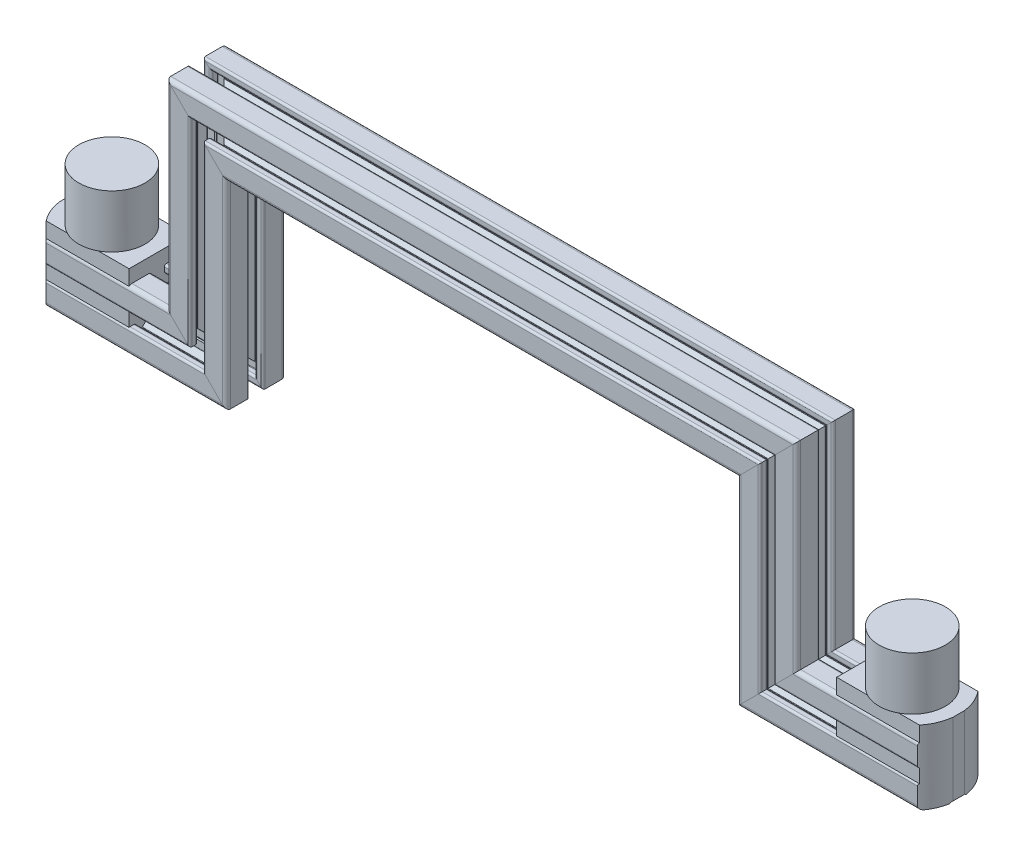
SolidWorks part; units mm, degrees
material "Commercially Pure CP-Ti UNS R50400 (SS)"
ref_plane "Front Plane" through (0, 0, 0) normal (0, 0, 1) x (1, 0, 0)
ref_plane "Top Plane" through (0, 0, 0) normal (0, 1, 0) x (1, 0, 0)
ref_plane "Right Plane" through (0, 0, 0) normal (1, 0, 0) x (0, 0, -1)
sketch "Sketch7" plane through (0, 0, 0) normal (1, 0, 0) x (0, 0, -1)
  line L0 (13.9698, 21.2743) -> (13.5298, 21.2743)
  line L1 (12.0298, 22.7743) -> (12.0298, 23.2743)
  line L2 (13.5298, 24.7743) -> (23.1398, 24.7743)
  line L3 (25.4198, 22.4943) -> (25.4198, 12.8843)
  line L4 (23.9198, 11.3843) -> (23.4198, 11.3843)
  line L5 (21.9198, 12.8843) -> (21.9198, 13.3243)
  line L6 (20.9198, 14.3243) -> (15.3498, 14.3243)
  line L7 (14.9698, 14.7043) -> (14.9698, 20.2743)
  line L8 (21.9589, -6.6897) -> (21.9589, -6.2497)
  line L9 (23.4589, -4.7497) -> (23.9589, -4.7497)
  line L10 (25.4589, -6.2497) -> (25.4589, -15.8597)
  line L11 (23.1789, -18.1397) -> (13.5689, -18.1397)
  line L12 (12.0689, -16.6397) -> (12.0689, -16.1397)
  line L13 (13.5689, -14.6397) -> (14.0089, -14.6397)
  line L14 (15.0089, -13.6397) -> (15.0089, -8.0697)
  line L15 (15.3889, -7.6897) -> (20.9589, -7.6897)
  line L16 (-6.0052, -14.6787) -> (-5.5652, -14.6787)
  line L17 (-4.0652, -16.1787) -> (-4.0652, -16.6787)
  line L18 (-5.5652, -18.1787) -> (-15.1752, -18.1787)
  line L19 (-17.4552, -15.8987) -> (-17.4552, -6.2887)
  line L20 (-15.9552, -4.7887) -> (-15.4552, -4.7887)
  line L21 (-13.9552, -6.2887) -> (-13.9552, -6.7287)
  line L22 (-12.9552, -7.7287) -> (-7.3852, -7.7287)
  line L23 (-7.0052, -8.1087) -> (-7.0052, -13.6787)
  line L24 (1.8289, -2.4886) -> (1.4132, -2.3164)
  line L25 (-1.632, 0.7289) -> (-1.8042, 1.1447)
  line L26 (-1.804, 5.4512) -> (-1.6318, 5.867)
  line L27 (1.4134, 8.9121) -> (1.8292, 9.0843)
  line L28 (6.1358, 9.0842) -> (6.5515, 8.912)
  line L29 (9.5966, 5.8667) -> (9.7688, 5.451)
  line L30 (9.7687, 1.1444) -> (9.5965, 0.7287)
  line L31 (6.5512, -2.3165) -> (6.1355, -2.4887)
  line L32 (-13.9942, 13.2853) -> (-13.9942, 12.8453)
  line L33 (-15.4942, 11.3453) -> (-15.9942, 11.3453)
  line L34 (-17.4942, 12.8453) -> (-17.4942, 22.4553)
  line L35 (-15.2142, 24.7353) -> (-5.6042, 24.7353)
  line L36 (-4.1042, 23.2353) -> (-4.1042, 22.7353)
  line L37 (-5.6042, 21.2353) -> (-6.0442, 21.2353)
  line L38 (-7.0442, 20.2353) -> (-7.0442, 14.6653)
  line L39 (-7.4242, 14.2853) -> (-12.9942, 14.2853)
  line L40 (4.9058, 11.2153) -> (4.0058, 10.7002)
  line L41 (4.0058, 10.7002) -> (3.1058, 11.2153)
  line L42 (3.1058, 11.2153) -> (-2.1975, 11.2153)
  line L43 (-2.4662, 11.3266) -> (-5.9329, 14.7933)
  line L44 (-6.0442, 15.062) -> (-6.0442, 19.3553)
  line L45 (-5.6642, 19.7353) -> (-2.5792, 19.7353)
  line L46 (-1.0592, 21.2553) -> (-1.0592, 24.2153)
  line L47 (-2.5792, 25.7353) -> (-15.4942, 25.7353)
  line L48 (-18.4942, 22.7353) -> (-18.4942, 9.8203)
  line L49 (-16.9742, 8.3003) -> (-14.0142, 8.3003)
  line L50 (-12.4942, 9.8203) -> (-12.4942, 12.9053)
  line L51 (-12.1142, 13.2853) -> (-7.8138, 13.2853)
  line L52 (-7.5451, 13.174) -> (-4.0855, 9.7144)
  line L53 (-3.9742, 9.4457) -> (-3.9742, 4.1353)
  line L54 (-3.9742, 4.1353) -> (-3.4546, 3.2353)
  line L55 (-3.4546, 3.2353) -> (-3.9742, 2.3353)
  line L56 (-3.9742, 2.3353) -> (-3.9742, -2.968)
  line L57 (-4.0855, -3.2367) -> (-7.5522, -6.7034)
  line L58 (-7.8209, -6.8147) -> (-12.1142, -6.8147)
  line L59 (-12.4942, -6.4347) -> (-12.4942, -3.3497)
  line L60 (-14.0142, -1.8297) -> (-16.9742, -1.8297)
  line L61 (-18.4942, -3.3497) -> (-18.4942, -16.2647)
  line L62 (-15.4942, -19.2647) -> (-2.5792, -19.2647)
  line L63 (-1.0592, -17.7447) -> (-1.0592, -14.7847)
  line L64 (-2.5792, -13.2647) -> (-5.6642, -13.2647)
  line L65 (-6.0442, -12.8847) -> (-6.0442, -8.5843)
  line L66 (-5.9329, -8.3156) -> (-2.4733, -4.856)
  line L67 (-2.2046, -4.7447) -> (3.1058, -4.7447)
  line L68 (3.1058, -4.7447) -> (4.0058, -4.2295)
  line L69 (4.0058, -4.2295) -> (4.9058, -4.7447)
  line L70 (4.9058, -4.7447) -> (10.2091, -4.7447)
  line L71 (10.4778, -4.856) -> (13.9445, -8.3227)
  line L72 (14.0558, -8.5914) -> (14.0558, -12.8847)
  line L73 (13.6758, -13.2647) -> (10.5908, -13.2647)
  line L74 (9.0708, -14.7847) -> (9.0708, -17.7447)
  line L75 (10.5908, -19.2647) -> (23.5058, -19.2647)
  line L76 (26.5058, -16.2647) -> (26.5058, -3.3497)
  line L77 (24.9858, -1.8297) -> (22.0258, -1.8297)
  line L78 (20.5058, -3.3497) -> (20.5058, -6.4347)
  line L79 (20.1258, -6.8147) -> (15.8254, -6.8147)
  line L80 (15.5567, -6.7034) -> (12.0971, -3.2438)
  line L81 (11.9858, -2.9751) -> (11.9858, 2.3353)
  line L82 (11.9858, 2.3353) -> (11.4662, 3.2353)
  line L83 (11.4662, 3.2353) -> (11.9858, 4.1353)
  line L84 (11.9858, 4.1353) -> (11.9858, 9.4386)
  line L85 (12.0971, 9.7073) -> (15.5638, 13.174)
  line L86 (15.8325, 13.2853) -> (20.1258, 13.2853)
  line L87 (20.5058, 12.9053) -> (20.5058, 9.8203)
  line L88 (22.0258, 8.3003) -> (24.9858, 8.3003)
  line L89 (26.5058, 9.8203) -> (26.5058, 22.7353)
  line L90 (23.5058, 25.7353) -> (10.5908, 25.7353)
  line L91 (9.0708, 24.2153) -> (9.0708, 21.2553)
  line L92 (10.5908, 19.7353) -> (13.6758, 19.7353)
  line L93 (14.0558, 19.3553) -> (14.0558, 15.0549)
  line L94 (13.9445, 14.7862) -> (10.4849, 11.3266)
  line L95 (10.2162, 11.2153) -> (4.9058, 11.2153)
  arc A0 (14.9698, 20.2743) -> (13.9698, 21.2743) centre (13.9698, 20.2743) ccw
  arc A1 (12.0298, 22.7743) -> (13.5298, 21.2743) centre (13.5298, 22.7743) ccw
  arc A2 (13.5298, 24.7743) -> (12.0298, 23.2743) centre (13.5298, 23.2743) ccw
  arc A3 (25.4198, 22.4943) -> (23.1398, 24.7743) centre (23.1398, 22.4943) ccw
  arc A4 (23.9198, 11.3843) -> (25.4198, 12.8843) centre (23.9198, 12.8843) ccw
  arc A5 (21.9198, 12.8843) -> (23.4198, 11.3843) centre (23.4198, 12.8843) ccw
  arc A6 (21.9198, 13.3243) -> (20.9198, 14.3243) centre (20.9198, 13.3243) ccw
  arc A7 (14.9698, 14.7043) -> (15.3498, 14.3243) centre (15.3498, 14.7043) ccw
  arc A8 (20.9589, -7.6897) -> (21.9589, -6.6897) centre (20.9589, -6.6897) ccw
  arc A9 (23.4589, -4.7497) -> (21.9589, -6.2497) centre (23.4589, -6.2497) ccw
  arc A10 (25.4589, -6.2497) -> (23.9589, -4.7497) centre (23.9589, -6.2497) ccw
  arc A11 (23.1789, -18.1397) -> (25.4589, -15.8597) centre (23.1789, -15.8597) ccw
  arc A12 (12.0689, -16.6397) -> (13.5689, -18.1397) centre (13.5689, -16.6397) ccw
  arc A13 (13.5689, -14.6397) -> (12.0689, -16.1397) centre (13.5689, -16.1397) ccw
  arc A14 (14.0089, -14.6397) -> (15.0089, -13.6397) centre (14.0089, -13.6397) ccw
  arc A15 (15.3889, -7.6897) -> (15.0089, -8.0697) centre (15.3889, -8.0697) ccw
  arc A16 (-7.0052, -13.6787) -> (-6.0052, -14.6787) centre (-6.0052, -13.6787) ccw
  arc A17 (-4.0652, -16.1787) -> (-5.5652, -14.6787) centre (-5.5652, -16.1787) ccw
  arc A18 (-5.5652, -18.1787) -> (-4.0652, -16.6787) centre (-5.5652, -16.6787) ccw
  arc A19 (-17.4552, -15.8987) -> (-15.1752, -18.1787) centre (-15.1752, -15.8987) ccw
  arc A20 (-15.9552, -4.7887) -> (-17.4552, -6.2887) centre (-15.9552, -6.2887) ccw
  arc A21 (-13.9552, -6.2887) -> (-15.4552, -4.7887) centre (-15.4552, -6.2887) ccw
  arc A22 (-13.9552, -6.7287) -> (-12.9552, -7.7287) centre (-12.9552, -6.7287) ccw
  arc A23 (-7.0052, -8.1087) -> (-7.3852, -7.7287) centre (-7.3852, -8.1087) ccw
  arc A24 (1.0363, -0.7421) -> (1.4132, -2.3164) centre (1.7959, -1.3925) ccw
  arc A25 (-0.0577, 0.352) -> (1.0363, -0.7421) centre (3.9823, 3.2978) ccw
  arc A26 (-1.632, 0.7289) -> (-0.0577, 0.352) centre (-0.7081, 1.1116) ccw
  arc A27 (-0.9575, 2.5244) -> (-1.8042, 1.1447) centre (-0.8803, 1.5274) ccw
  arc A28 (-0.9574, 4.0715) -> (-0.9575, 2.5244) centre (3.9823, 3.2978) ccw
  arc A29 (-1.804, 5.4512) -> (-0.9574, 4.0715) centre (-0.8802, 5.0686) ccw
  arc A30 (-0.0575, 6.2439) -> (-1.6318, 5.867) centre (-0.708, 5.4843) ccw
  arc A31 (1.0365, 7.3379) -> (-0.0575, 6.2439) centre (3.9823, 3.2978) ccw
  arc A32 (1.4134, 8.9121) -> (1.0365, 7.3379) centre (1.7961, 7.9882) ccw
  arc A33 (3.2089, 8.2376) -> (1.8292, 9.0843) centre (2.2119, 8.1604) ccw
  arc A34 (4.7561, 8.2376) -> (3.2089, 8.2376) centre (3.9823, 3.2978) ccw
  arc A35 (6.1358, 9.0842) -> (4.7561, 8.2376) centre (5.7531, 8.1603) ccw
  arc A36 (6.9284, 7.3377) -> (6.5515, 8.912) centre (6.1688, 7.9881) ccw
  arc A37 (8.0224, 6.2437) -> (6.9284, 7.3377) centre (3.9823, 3.2978) ccw
  arc A38 (9.5966, 5.8667) -> (8.0224, 6.2437) centre (8.6727, 5.484) ccw
  arc A39 (8.9222, 4.0713) -> (9.7688, 5.451) centre (8.845, 5.0683) ccw
  arc A40 (8.9221, 2.5241) -> (8.9222, 4.0713) centre (3.9823, 3.2978) ccw
  arc A41 (9.7687, 1.1444) -> (8.9221, 2.5241) centre (8.8448, 1.5271) ccw
  arc A42 (8.0222, 0.3518) -> (9.5965, 0.7287) centre (8.6726, 1.1113) ccw
  arc A43 (6.9282, -0.7422) -> (8.0222, 0.3518) centre (3.9823, 3.2978) ccw
  arc A44 (6.5512, -2.3165) -> (6.9282, -0.7422) centre (6.1685, -1.3926) ccw
  arc A45 (4.7558, -1.642) -> (6.1355, -2.4887) centre (5.7528, -1.5648) ccw
  arc A46 (3.2086, -1.642) -> (4.7558, -1.642) centre (3.9823, 3.2978) ccw
  arc A47 (1.8289, -2.4886) -> (3.2086, -1.642) centre (2.2116, -1.5647) ccw
  arc A48 (-12.9942, 14.2853) -> (-13.9942, 13.2853) centre (-12.9942, 13.2853) ccw
  arc A49 (-15.4942, 11.3453) -> (-13.9942, 12.8453) centre (-15.4942, 12.8453) ccw
  arc A50 (-17.4942, 12.8453) -> (-15.9942, 11.3453) centre (-15.9942, 12.8453) ccw
  arc A51 (-15.2142, 24.7353) -> (-17.4942, 22.4553) centre (-15.2142, 22.4553) ccw
  arc A52 (-4.1042, 23.2353) -> (-5.6042, 24.7353) centre (-5.6042, 23.2353) ccw
  arc A53 (-5.6042, 21.2353) -> (-4.1042, 22.7353) centre (-5.6042, 22.7353) ccw
  arc A54 (-6.0442, 21.2353) -> (-7.0442, 20.2353) centre (-6.0442, 20.2353) ccw
  arc A55 (-7.4242, 14.2853) -> (-7.0442, 14.6653) centre (-7.4242, 14.6653) ccw
  arc A56 (-2.4662, 11.3266) -> (-2.1975, 11.2153) centre (-2.1975, 11.5953) ccw
  arc A57 (-6.0442, 15.062) -> (-5.9329, 14.7933) centre (-5.6642, 15.062) ccw
  arc A58 (-5.6642, 19.7353) -> (-6.0442, 19.3553) centre (-5.6642, 19.3553) ccw
  arc A59 (-2.5792, 19.7353) -> (-1.0592, 21.2553) centre (-2.5792, 21.2553) ccw
  arc A60 (-1.0592, 24.2153) -> (-2.5792, 25.7353) centre (-2.5792, 24.2153) ccw
  arc A61 (-15.4942, 25.7353) -> (-18.4942, 22.7353) centre (-15.4942, 22.7353) ccw
  arc A62 (-18.4942, 9.8203) -> (-16.9742, 8.3003) centre (-16.9742, 9.8203) ccw
  arc A63 (-14.0142, 8.3003) -> (-12.4942, 9.8203) centre (-14.0142, 9.8203) ccw
  arc A64 (-12.1142, 13.2853) -> (-12.4942, 12.9053) centre (-12.1142, 12.9053) ccw
  arc A65 (-7.5451, 13.174) -> (-7.8138, 13.2853) centre (-7.8138, 12.9053) ccw
  arc A66 (-3.9742, 9.4457) -> (-4.0855, 9.7144) centre (-4.3542, 9.4457) ccw
  arc A67 (-4.0855, -3.2367) -> (-3.9742, -2.968) centre (-4.3542, -2.968) ccw
  arc A68 (-7.8209, -6.8147) -> (-7.5522, -6.7034) centre (-7.8209, -6.4347) ccw
  arc A69 (-12.4942, -6.4347) -> (-12.1142, -6.8147) centre (-12.1142, -6.4347) ccw
  arc A70 (-12.4942, -3.3497) -> (-14.0142, -1.8297) centre (-14.0142, -3.3497) ccw
  arc A71 (-16.9742, -1.8297) -> (-18.4942, -3.3497) centre (-16.9742, -3.3497) ccw
  arc A72 (-18.4942, -16.2647) -> (-15.4942, -19.2647) centre (-15.4942, -16.2647) ccw
  arc A73 (-2.5792, -19.2647) -> (-1.0592, -17.7447) centre (-2.5792, -17.7447) ccw
  arc A74 (-1.0592, -14.7847) -> (-2.5792, -13.2647) centre (-2.5792, -14.7847) ccw
  arc A75 (-6.0442, -12.8847) -> (-5.6642, -13.2647) centre (-5.6642, -12.8847) ccw
  arc A76 (-5.9329, -8.3156) -> (-6.0442, -8.5843) centre (-5.6642, -8.5843) ccw
  arc A77 (-2.2046, -4.7447) -> (-2.4733, -4.856) centre (-2.2046, -5.1247) ccw
  arc A78 (10.4778, -4.856) -> (10.2091, -4.7447) centre (10.2091, -5.1247) ccw
  arc A79 (14.0558, -8.5914) -> (13.9445, -8.3227) centre (13.6758, -8.5914) ccw
  arc A80 (13.6758, -13.2647) -> (14.0558, -12.8847) centre (13.6758, -12.8847) ccw
  arc A81 (10.5908, -13.2647) -> (9.0708, -14.7847) centre (10.5908, -14.7847) ccw
  arc A82 (9.0708, -17.7447) -> (10.5908, -19.2647) centre (10.5908, -17.7447) ccw
  arc A83 (23.5058, -19.2647) -> (26.5058, -16.2647) centre (23.5058, -16.2647) ccw
  arc A84 (26.5058, -3.3497) -> (24.9858, -1.8297) centre (24.9858, -3.3497) ccw
  arc A85 (22.0258, -1.8297) -> (20.5058, -3.3497) centre (22.0258, -3.3497) ccw
  arc A86 (20.1258, -6.8147) -> (20.5058, -6.4347) centre (20.1258, -6.4347) ccw
  arc A87 (15.5567, -6.7034) -> (15.8254, -6.8147) centre (15.8254, -6.4347) ccw
  arc A88 (11.9858, -2.9751) -> (12.0971, -3.2438) centre (12.3658, -2.9751) ccw
  arc A89 (12.0971, 9.7073) -> (11.9858, 9.4386) centre (12.3658, 9.4386) ccw
  arc A90 (15.8325, 13.2853) -> (15.5638, 13.174) centre (15.8325, 12.9053) ccw
  arc A91 (20.5058, 12.9053) -> (20.1258, 13.2853) centre (20.1258, 12.9053) ccw
  arc A92 (20.5058, 9.8203) -> (22.0258, 8.3003) centre (22.0258, 9.8203) ccw
  arc A93 (24.9858, 8.3003) -> (26.5058, 9.8203) centre (24.9858, 9.8203) ccw
  arc A94 (26.5058, 22.7353) -> (23.5058, 25.7353) centre (23.5058, 22.7353) ccw
  arc A95 (10.5908, 25.7353) -> (9.0708, 24.2153) centre (10.5908, 24.2153) ccw
  arc A96 (9.0708, 21.2553) -> (10.5908, 19.7353) centre (10.5908, 21.2553) ccw
  arc A97 (14.0558, 19.3553) -> (13.6758, 19.7353) centre (13.6758, 19.3553) ccw
  arc A98 (13.9445, 14.7862) -> (14.0558, 15.0549) centre (13.6758, 15.0549) ccw
  arc A99 (10.2162, 11.2153) -> (10.4849, 11.3266) centre (10.2162, 11.5953) ccw
sketch "Sketch1" plane through (0, 0, 0) normal (0, 0, 1) x (1, 0, 0)
  line L0 (0, 0) -> (125, 0)
  line L1 (125, 0) -> (125, 150)
  line L2 (125, 150) -> (337, 150)
  dimension "D1" = 337
  dimension "D2" = 125
  dimension "D3" = 150
sketch "Sketch2" [suppressed] plane through (0, 0, 0) normal (1, 0, 0) x (0, 0, -1)
  line L0 (-33.5, -41) -> (-31.5, -41)
  line L1 (-31.5, -43) -> (-42, -43)
  line L2 (-43, -42) -> (-43, -31.5)
  line L3 (-41, -31.5) -> (-41, -33.5)
  line L4 (-40, -34.5) -> (-34.88, -34.5)
  line L5 (-34.5, -34.88) -> (-34.5, -40)
  line L6 (-16.657, -26.2238) -> (-18.284, -25.188)
  line L7 (-19.8123, -26.7162) -> (-18.7764, -28.3429)
  line L8 (-21.0015, -29.2647) -> (-21.4195, -27.3819)
  line L9 (-23.5808, -27.3818) -> (-23.9986, -29.2645)
  line L10 (-26.2238, -28.343) -> (-25.188, -26.716)
  line L11 (-26.7162, -25.1877) -> (-28.3429, -26.2236)
  line L12 (-29.2647, -23.9985) -> (-27.3819, -23.5805)
  line L13 (-27.3818, -21.4192) -> (-29.2645, -21.0014)
  line L14 (-28.343, -18.7762) -> (-26.716, -19.812)
  line L15 (-25.1877, -18.2838) -> (-26.2236, -16.6571)
  line L16 (-23.9985, -15.7353) -> (-23.5805, -17.6181)
  line L17 (-21.4192, -17.6182) -> (-21.0014, -15.7355)
  line L18 (-18.7762, -16.657) -> (-19.812, -18.284)
  line L19 (-18.2838, -19.8123) -> (-16.6571, -18.7764)
  line L20 (-15.7353, -21.0015) -> (-17.6181, -21.4195)
  line L21 (-17.6182, -23.5808) -> (-15.7355, -23.9986)
  line L22 (41, -33.5) -> (41, -31.5)
  line L23 (43, -31.5) -> (43, -42)
  line L24 (42, -43) -> (31.5, -43)
  line L25 (31.5, -41) -> (33.5, -41)
  line L26 (34.5, -40) -> (34.5, -34.88)
  line L27 (34.88, -34.5) -> (40, -34.5)
  line L28 (26.7162, -19.8123) -> (28.3429, -18.7764)
  line L29 (29.2647, -21.0015) -> (27.3819, -21.4195)
  line L30 (27.3818, -23.5808) -> (29.2645, -23.9986)
  line L31 (28.343, -26.2238) -> (26.716, -25.188)
  line L32 (25.1877, -26.7162) -> (26.2236, -28.3429)
  line L33 (23.9985, -29.2647) -> (23.5805, -27.3819)
  line L34 (21.4192, -27.3818) -> (21.0014, -29.2645)
  line L35 (18.7762, -28.343) -> (19.812, -26.716)
  line L36 (18.2838, -25.1877) -> (16.6571, -26.2236)
  line L37 (15.7353, -23.9985) -> (17.6181, -23.5805)
  line L38 (17.6182, -21.4192) -> (15.7355, -21.0014)
  line L39 (16.657, -18.7762) -> (18.284, -19.812)
  line L40 (19.8123, -18.2838) -> (18.7764, -16.6571)
  line L41 (21.0015, -15.7353) -> (21.4195, -17.6181)
  line L42 (23.5808, -17.6182) -> (23.9986, -15.7355)
  line L43 (26.2238, -16.657) -> (25.188, -18.284)
  line L44 (34.5, 34.88) -> (34.5, 40)
  line L45 (33.5, 41) -> (31.5, 41)
  line L46 (31.5, 43) -> (42, 43)
  line L47 (43, 42) -> (43, 31.5)
  line L48 (41, 31.5) -> (41, 33.5)
  line L49 (40, 34.5) -> (34.88, 34.5)
  line L50 (26.7162, 25.1877) -> (28.3429, 26.2236)
  line L51 (29.2647, 23.9985) -> (27.3819, 23.5805)
  line L52 (27.3818, 21.4192) -> (29.2645, 21.0014)
  line L53 (28.343, 18.7762) -> (26.716, 19.812)
  line L54 (25.1877, 18.2838) -> (26.2236, 16.6571)
  line L55 (23.9985, 15.7353) -> (23.5805, 17.6181)
  line L56 (21.4192, 17.6182) -> (21.0014, 15.7355)
  line L57 (18.7762, 16.657) -> (19.812, 18.284)
  line L58 (18.2838, 19.8123) -> (16.6571, 18.7764)
  line L59 (15.7353, 21.0015) -> (17.6181, 21.4195)
  line L60 (17.6182, 23.5808) -> (15.7355, 23.9986)
  line L61 (16.657, 26.2238) -> (18.284, 25.188)
  line L62 (19.8123, 26.7162) -> (18.7764, 28.3429)
  line L63 (21.0015, 29.2647) -> (21.4195, 27.3819)
  line L64 (23.5808, 27.3818) -> (23.9986, 29.2645)
  line L65 (26.2238, 28.343) -> (25.188, 26.716)
  line L66 (-41, 33.5) -> (-41, 31.5)
  line L67 (-43, 31.5) -> (-43, 42)
  line L68 (-42, 43) -> (-31.5, 43)
  line L69 (-31.5, 41) -> (-33.5, 41)
  line L70 (-34.5, 40) -> (-34.5, 34.88)
  line L71 (-34.88, 34.5) -> (-40, 34.5)
  line L72 (-16.657, 18.7762) -> (-18.284, 19.812)
  line L73 (-19.8123, 18.2838) -> (-18.7764, 16.6571)
  line L74 (-21.0015, 15.7353) -> (-21.4195, 17.6181)
  line L75 (-23.5808, 17.6182) -> (-23.9986, 15.7355)
  line L76 (-26.2238, 16.657) -> (-25.188, 18.284)
  line L77 (-26.7162, 19.8123) -> (-28.3429, 18.7764)
  line L78 (-29.2647, 21.0015) -> (-27.3819, 21.4195)
  line L79 (-27.3818, 23.5808) -> (-29.2645, 23.9986)
  line L80 (-28.343, 26.2238) -> (-26.716, 25.188)
  line L81 (-25.1877, 26.7162) -> (-26.2236, 28.3429)
  line L82 (-23.9985, 29.2647) -> (-23.5805, 27.3819)
  line L83 (-21.4192, 27.3818) -> (-21.0014, 29.2645)
  line L84 (-18.7762, 28.343) -> (-19.812, 26.716)
  line L85 (-18.2838, 25.1877) -> (-16.6571, 26.2236)
  line L86 (-15.7353, 23.9985) -> (-17.6181, 23.5805)
  line L87 (-17.6182, 21.4192) -> (-15.7355, 21.0014)
  line L88 (39, -10.16) -> (33.3774, -10.16)
  line L89 (31.9632, -10.7458) -> (29.8203, -12.8887)
  line L90 (29.5516, -13) -> (23.4, -13)
  line L91 (23.4, -13) -> (22.5, -13.5151)
  line L92 (22.5, -13.5151) -> (21.6, -13)
  line L93 (21.6, -13) -> (15, -13)
  line L94 (13, -15) -> (13, -21.6)
  line L95 (13, -21.6) -> (13.5196, -22.5)
  line L96 (13.5196, -22.5) -> (13, -23.4)
  line L97 (13, -23.4) -> (13, -29.5516)
  line L98 (12.8887, -29.8203) -> (11.3787, -31.3303)
  line L99 (10.5, -33.4516) -> (10.5, -40)
  line L100 (11.5, -41) -> (13.5, -41)
  line L101 (13.5, -43) -> (-13.5, -43)
  line L102 (-13.5, -41) -> (-11.5, -41)
  line L103 (-10.5, -40) -> (-10.5, -33.4516)
  line L104 (-11.3787, -31.3303) -> (-12.8887, -29.8203)
  line L105 (-13, -29.5516) -> (-13, -23.4)
  line L106 (-13, -23.4) -> (-13.5196, -22.5)
  line L107 (-13.5196, -22.5) -> (-13, -21.6)
  line L108 (-13, -21.6) -> (-13, -15)
  line L109 (-15, -13) -> (-21.6, -13)
  line L110 (-21.6, -13) -> (-22.5, -13.5151)
  line L111 (-22.5, -13.5151) -> (-23.4, -13)
  line L112 (-23.4, -13) -> (-29.5516, -13)
  line L113 (-29.8203, -12.8887) -> (-31.9632, -10.7458)
  line L114 (-33.3774, -10.16) -> (-39, -10.16)
  line L115 (-41, -12.16) -> (-41, -13.5)
  line L116 (-43, -13.5) -> (-43, 13.5)
  line L117 (-41, 13.5) -> (-41, 12.16)
  line L118 (-39, 10.16) -> (-33.3774, 10.16)
  line L119 (-31.9632, 10.7458) -> (-29.8203, 12.8887)
  line L120 (-29.5516, 13) -> (-23.4, 13)
  line L121 (-23.4, 13) -> (-22.5, 13.5151)
  line L122 (-22.5, 13.5151) -> (-21.6, 13)
  line L123 (-21.6, 13) -> (-15, 13)
  line L124 (-13, 15) -> (-13, 21.6)
  line L125 (-13, 21.6) -> (-13.5196, 22.5)
  line L126 (-13.5196, 22.5) -> (-13, 23.4)
  line L127 (-13, 23.4) -> (-13, 29.5516)
  line L128 (-12.8887, 29.8203) -> (-11.3787, 31.3303)
  line L129 (-10.5, 33.4516) -> (-10.5, 40)
  line L130 (-11.5, 41) -> (-13.5, 41)
  line L131 (-13.5, 43) -> (13.5, 43)
  line L132 (13.5, 41) -> (11.5, 41)
  line L133 (10.5, 40) -> (10.5, 33.4516)
  line L134 (11.3787, 31.3303) -> (12.8887, 29.8203)
  line L135 (13, 29.5516) -> (13, 23.4)
  line L136 (13, 23.4) -> (13.5196, 22.5)
  line L137 (13.5196, 22.5) -> (13, 21.6)
  line L138 (13, 21.6) -> (13, 15)
  line L139 (15, 13) -> (21.6, 13)
  line L140 (21.6, 13) -> (22.5, 13.5151)
  line L141 (22.5, 13.5151) -> (23.4, 13)
  line L142 (23.4, 13) -> (29.5516, 13)
  line L143 (29.8203, 12.8887) -> (31.9581, 10.7509)
  line L144 (33.3723, 10.1651) -> (39, 10.1651)
  line L145 (41, 12.1651) -> (41, 13.5)
  line L146 (43, 13.5) -> (43, -13.5)
  line L147 (41, -13.5) -> (41, -12.16)
  line L148 (45, -15.915) -> (45, 15.915)
  line L149 (43.48, 17.435) -> (40.52, 17.435)
  line L150 (39, 15.915) -> (39, 13.45)
  line L151 (38, 12.45) -> (34.9984, 12.45)
  line L152 (34.7297, 12.5613) -> (32.1113, 15.1797)
  line L153 (32, 15.4484) -> (32, 21.6)
  line L154 (32, 21.6) -> (31.4804, 22.5)
  line L155 (31.4804, 22.5) -> (32, 23.4)
  line L156 (32, 23.4) -> (32, 29.5516)
  line L157 (32.1113, 29.8203) -> (34.7297, 32.4387)
  line L158 (34.9984, 32.55) -> (38, 32.55)
  line L159 (39, 31.55) -> (39, 29.085)
  line L160 (40.52, 27.565) -> (43.48, 27.565)
  line L161 (45, 29.085) -> (45, 42)
  line L162 (42, 45) -> (29.085, 45)
  line L163 (27.565, 43.48) -> (27.565, 40.52)
  line L164 (29.085, 39) -> (31.55, 39)
  line L165 (32.55, 38) -> (32.55, 34.9984)
  line L166 (32.4387, 34.7297) -> (29.8203, 32.1113)
  line L167 (29.5516, 32) -> (23.4, 32)
  line L168 (23.4, 32) -> (22.5, 31.4849)
  line L169 (22.5, 31.4849) -> (21.6, 32)
  line L170 (21.6, 32) -> (15.4484, 32)
  line L171 (15.1797, 32.1113) -> (12.5613, 34.7297)
  line L172 (12.45, 34.9984) -> (12.45, 38)
  line L173 (13.45, 39) -> (15.915, 39)
  line L174 (17.435, 40.52) -> (17.435, 43.48)
  line L175 (15.915, 45) -> (-15.915, 45)
  line L176 (-17.435, 43.48) -> (-17.435, 40.52)
  line L177 (-15.915, 39) -> (-13.45, 39)
  line L178 (-12.45, 38) -> (-12.45, 34.9984)
  line L179 (-12.5613, 34.7297) -> (-15.1797, 32.1113)
  line L180 (-15.4484, 32) -> (-21.6, 32)
  line L181 (-21.6, 32) -> (-22.5, 31.4849)
  line L182 (-22.5, 31.4849) -> (-23.4, 32)
  line L183 (-23.4, 32) -> (-29.5516, 32)
  line L184 (-29.8203, 32.1113) -> (-32.4387, 34.7297)
  line L185 (-32.55, 34.9984) -> (-32.55, 38)
  line L186 (-31.55, 39) -> (-29.085, 39)
  line L187 (-27.565, 40.52) -> (-27.565, 43.48)
  line L188 (-29.085, 45) -> (-42, 45)
  line L189 (-45, 42) -> (-45, 29.085)
  line L190 (-43.48, 27.565) -> (-40.52, 27.565)
  line L191 (-39, 29.085) -> (-39, 31.55)
  line L192 (-38, 32.55) -> (-34.9984, 32.55)
  line L193 (-34.7297, 32.4387) -> (-32.1113, 29.8203)
  line L194 (-32, 29.5516) -> (-32, 23.4)
  line L195 (-32, 23.4) -> (-31.4804, 22.5)
  line L196 (-31.4804, 22.5) -> (-32, 21.6)
  line L197 (-32, 21.6) -> (-32, 15.4484)
  line L198 (-32.1113, 15.1797) -> (-34.7297, 12.5613)
  line L199 (-34.9984, 12.45) -> (-38, 12.45)
  line L200 (-39, 13.45) -> (-39, 15.915)
  line L201 (-40.52, 17.435) -> (-43.48, 17.435)
  line L202 (-45, 15.915) -> (-45, -15.915)
  line L203 (-43.48, -17.435) -> (-40.52, -17.435)
  line L204 (-39, -15.915) -> (-39, -13.45)
  line L205 (-38, -12.45) -> (-34.9984, -12.45)
  line L206 (-34.7297, -12.5613) -> (-32.1113, -15.1797)
  line L207 (-32, -15.4484) -> (-32, -21.6)
  line L208 (-32, -21.6) -> (-31.4804, -22.5)
  line L209 (-31.4804, -22.5) -> (-32, -23.4)
  line L210 (-32, -23.4) -> (-32, -29.5516)
  line L211 (-32.1113, -29.8203) -> (-34.7297, -32.4387)
  line L212 (-34.9984, -32.55) -> (-38, -32.55)
  line L213 (-39, -31.55) -> (-39, -29.085)
  line L214 (-40.52, -27.565) -> (-43.48, -27.565)
  line L215 (-45, -29.085) -> (-45, -42)
  line L216 (-42, -45) -> (-29.085, -45)
  line L217 (-27.565, -43.48) -> (-27.565, -40.52)
  line L218 (-29.085, -39) -> (-31.55, -39)
  line L219 (-32.55, -38) -> (-32.55, -34.9984)
  line L220 (-32.4387, -34.7297) -> (-29.8203, -32.1113)
  line L221 (-29.5516, -32) -> (-23.4, -32)
  line L222 (-23.4, -32) -> (-22.5, -31.4849)
  line L223 (-22.5, -31.4849) -> (-21.6, -32)
  line L224 (-21.6, -32) -> (-15.4484, -32)
  line L225 (-15.1797, -32.1113) -> (-12.5613, -34.7297)
  line L226 (-12.45, -34.9984) -> (-12.45, -38)
  line L227 (-13.45, -39) -> (-15.915, -39)
  line L228 (-17.435, -40.52) -> (-17.435, -43.48)
  line L229 (-15.915, -45) -> (15.915, -45)
  line L230 (17.435, -43.48) -> (17.435, -40.52)
  line L231 (15.915, -39) -> (13.45, -39)
  line L232 (12.45, -38) -> (12.45, -34.9984)
  line L233 (12.5613, -34.7297) -> (15.1797, -32.1113)
  line L234 (15.4484, -32) -> (21.6, -32)
  line L235 (21.6, -32) -> (22.5, -31.4849)
  line L236 (22.5, -31.4849) -> (23.4, -32)
  line L237 (23.4, -32) -> (29.5516, -32)
  line L238 (29.8203, -32.1113) -> (32.4387, -34.7297)
  line L239 (32.55, -34.9984) -> (32.55, -38)
  line L240 (31.55, -39) -> (29.085, -39)
  line L241 (27.565, -40.52) -> (27.565, -43.48)
  line L242 (29.085, -45) -> (42, -45)
  line L243 (45, -42) -> (45, -29.085)
  line L244 (43.48, -27.565) -> (40.52, -27.565)
  line L245 (39, -29.085) -> (39, -31.55)
  line L246 (38, -32.55) -> (34.9984, -32.55)
  line L247 (34.7297, -32.4387) -> (32.1113, -29.8203)
  line L248 (32, -29.5516) -> (32, -23.4)
  line L249 (32, -23.4) -> (31.4804, -22.5)
  line L250 (31.4804, -22.5) -> (32, -21.6)
  line L251 (32, -21.6) -> (32, -15.4484)
  line L252 (32.1113, -15.1797) -> (34.7297, -12.5613)
  line L253 (34.9984, -12.45) -> (38, -12.45)
  line L254 (39, -13.45) -> (39, -15.915)
  line L255 (40.52, -17.435) -> (43.48, -17.435)
  arc A0 (-34.5, -40) -> (-33.5, -41) centre (-33.5, -40) ccw
  arc A1 (-31.5, -43) -> (-31.5, -41) centre (-31.5, -42) ccw
  arc A2 (-43, -42) -> (-42, -43) centre (-42, -42) ccw
  arc A3 (-41, -31.5) -> (-43, -31.5) centre (-42, -31.5) ccw
  arc A4 (-41, -33.5) -> (-40, -34.5) centre (-40, -33.5) ccw
  arc A5 (-34.5, -34.88) -> (-34.88, -34.5) centre (-34.88, -34.88) ccw
  arc A6 (-15.2086, -25.7917) -> (-15.0167, -25.3284) centre (-22.5, -22.5) ccw
  arc A7 (-16.657, -26.2238) -> (-15.2086, -25.7917) centre (-16.12, -25.3802) ccw
  arc A8 (-19.8123, -26.7162) -> (-18.284, -25.188) centre (-22.5, -22.5) ccw
  arc A9 (-19.2085, -29.7915) -> (-18.7764, -28.3429) centre (-19.6199, -28.8801) ccw
  arc A10 (-19.6717, -29.9834) -> (-19.2085, -29.7915) centre (-22.5, -22.5) ccw
  arc A11 (-21.0015, -29.2647) -> (-19.6717, -29.9834) centre (-20.0253, -29.048) ccw
  arc A12 (-23.5808, -27.3818) -> (-21.4195, -27.3819) centre (-22.5, -22.5) ccw
  arc A13 (-25.3284, -29.9833) -> (-23.9986, -29.2645) centre (-24.9749, -29.0479) ccw
  arc A14 (-25.7917, -29.7914) -> (-25.3284, -29.9833) centre (-22.5, -22.5) ccw
  arc A15 (-26.2238, -28.343) -> (-25.7917, -29.7914) centre (-25.3802, -28.88) ccw
  arc A16 (-26.7162, -25.1877) -> (-25.188, -26.716) centre (-22.5, -22.5) ccw
  arc A17 (-29.7915, -25.7915) -> (-28.3429, -26.2236) centre (-28.8801, -25.3801) ccw
  arc A18 (-29.9834, -25.3283) -> (-29.7915, -25.7915) centre (-22.5, -22.5) ccw
  arc A19 (-29.2647, -23.9985) -> (-29.9834, -25.3283) centre (-29.048, -24.9747) ccw
  arc A20 (-27.3818, -21.4192) -> (-27.3819, -23.5805) centre (-22.5, -22.5) ccw
  arc A21 (-29.9833, -19.6716) -> (-29.2645, -21.0014) centre (-29.0479, -20.0251) ccw
  arc A22 (-29.7914, -19.2083) -> (-29.9833, -19.6716) centre (-22.5, -22.5) ccw
  arc A23 (-28.343, -18.7762) -> (-29.7914, -19.2083) centre (-28.88, -19.6198) ccw
  arc A24 (-25.1877, -18.2838) -> (-26.716, -19.812) centre (-22.5, -22.5) ccw
  arc A25 (-25.7915, -15.2085) -> (-26.2236, -16.6571) centre (-25.3801, -16.1199) ccw
  arc A26 (-25.3283, -15.0166) -> (-25.7915, -15.2085) centre (-22.5, -22.5) ccw
  arc A27 (-23.9985, -15.7353) -> (-25.3283, -15.0166) centre (-24.9747, -15.952) ccw
  arc A28 (-21.4192, -17.6182) -> (-23.5805, -17.6181) centre (-22.5, -22.5) ccw
  arc A29 (-19.6716, -15.0167) -> (-21.0014, -15.7355) centre (-20.0251, -15.9521) ccw
  arc A30 (-19.2083, -15.2086) -> (-19.6716, -15.0167) centre (-22.5, -22.5) ccw
  arc A31 (-18.7762, -16.657) -> (-19.2083, -15.2086) centre (-19.6198, -16.12) ccw
  arc A32 (-18.2838, -19.8123) -> (-19.812, -18.284) centre (-22.5, -22.5) ccw
  arc A33 (-15.2085, -19.2085) -> (-16.6571, -18.7764) centre (-16.1199, -19.6199) ccw
  arc A34 (-15.0166, -19.6717) -> (-15.2085, -19.2085) centre (-22.5, -22.5) ccw
  arc A35 (-15.7353, -21.0015) -> (-15.0166, -19.6717) centre (-15.952, -20.0253) ccw
  arc A36 (-17.6182, -23.5808) -> (-17.6181, -21.4195) centre (-22.5, -22.5) ccw
  arc A37 (-15.0167, -25.3284) -> (-15.7355, -23.9986) centre (-15.9521, -24.9749) ccw
  arc A38 (40, -34.5) -> (41, -33.5) centre (40, -33.5) ccw
  arc A39 (43, -31.5) -> (41, -31.5) centre (42, -31.5) ccw
  arc A40 (42, -43) -> (43, -42) centre (42, -42) ccw
  arc A41 (31.5, -41) -> (31.5, -43) centre (31.5, -42) ccw
  arc A42 (33.5, -41) -> (34.5, -40) centre (33.5, -40) ccw
  arc A43 (34.88, -34.5) -> (34.5, -34.88) centre (34.88, -34.88) ccw
  arc A44 (26.7162, -19.8123) -> (25.188, -18.284) centre (22.5, -22.5) ccw
  arc A45 (29.7915, -19.2085) -> (28.3429, -18.7764) centre (28.8801, -19.6199) ccw
  arc A46 (29.9834, -19.6717) -> (29.7915, -19.2085) centre (22.5, -22.5) ccw
  arc A47 (29.2647, -21.0015) -> (29.9834, -19.6717) centre (29.048, -20.0253) ccw
  arc A48 (27.3818, -23.5808) -> (27.3819, -21.4195) centre (22.5, -22.5) ccw
  arc A49 (29.9833, -25.3284) -> (29.2645, -23.9986) centre (29.0479, -24.9749) ccw
  arc A50 (29.7914, -25.7917) -> (29.9833, -25.3284) centre (22.5, -22.5) ccw
  arc A51 (28.343, -26.2238) -> (29.7914, -25.7917) centre (28.88, -25.3802) ccw
  arc A52 (25.1877, -26.7162) -> (26.716, -25.188) centre (22.5, -22.5) ccw
  arc A53 (25.7915, -29.7915) -> (26.2236, -28.3429) centre (25.3801, -28.8801) ccw
  arc A54 (25.3283, -29.9834) -> (25.7915, -29.7915) centre (22.5, -22.5) ccw
  arc A55 (23.9985, -29.2647) -> (25.3283, -29.9834) centre (24.9747, -29.048) ccw
  arc A56 (21.4192, -27.3818) -> (23.5805, -27.3819) centre (22.5, -22.5) ccw
  arc A57 (19.6716, -29.9833) -> (21.0014, -29.2645) centre (20.0251, -29.0479) ccw
  arc A58 (19.2083, -29.7914) -> (19.6716, -29.9833) centre (22.5, -22.5) ccw
  arc A59 (18.7762, -28.343) -> (19.2083, -29.7914) centre (19.6198, -28.88) ccw
  arc A60 (18.2838, -25.1877) -> (19.812, -26.716) centre (22.5, -22.5) ccw
  arc A61 (15.2085, -25.7915) -> (16.6571, -26.2236) centre (16.1199, -25.3801) ccw
  arc A62 (15.0166, -25.3283) -> (15.2085, -25.7915) centre (22.5, -22.5) ccw
  arc A63 (15.7353, -23.9985) -> (15.0166, -25.3283) centre (15.952, -24.9747) ccw
  arc A64 (17.6182, -21.4192) -> (17.6181, -23.5805) centre (22.5, -22.5) ccw
  arc A65 (15.0167, -19.6716) -> (15.7355, -21.0014) centre (15.9521, -20.0251) ccw
  arc A66 (15.2086, -19.2083) -> (15.0167, -19.6716) centre (22.5, -22.5) ccw
  arc A67 (16.657, -18.7762) -> (15.2086, -19.2083) centre (16.12, -19.6198) ccw
  arc A68 (19.8123, -18.2838) -> (18.284, -19.812) centre (22.5, -22.5) ccw
  arc A69 (19.2085, -15.2085) -> (18.7764, -16.6571) centre (19.6199, -16.1199) ccw
  arc A70 (19.6717, -15.0166) -> (19.2085, -15.2085) centre (22.5, -22.5) ccw
  arc A71 (21.0015, -15.7353) -> (19.6717, -15.0166) centre (20.0253, -15.952) ccw
  arc A72 (23.5808, -17.6182) -> (21.4195, -17.6181) centre (22.5, -22.5) ccw
  arc A73 (25.3284, -15.0167) -> (23.9986, -15.7355) centre (24.9749, -15.9521) ccw
  arc A74 (25.7917, -15.2086) -> (25.3284, -15.0167) centre (22.5, -22.5) ccw
  arc A75 (26.2238, -16.657) -> (25.7917, -15.2086) centre (25.3802, -16.12) ccw
  arc A76 (34.5, 34.88) -> (34.88, 34.5) centre (34.88, 34.88) ccw
  arc A77 (34.5, 40) -> (33.5, 41) centre (33.5, 40) ccw
  arc A78 (31.5, 43) -> (31.5, 41) centre (31.5, 42) ccw
  arc A79 (43, 42) -> (42, 43) centre (42, 42) ccw
  arc A80 (41, 31.5) -> (43, 31.5) centre (42, 31.5) ccw
  arc A81 (41, 33.5) -> (40, 34.5) centre (40, 33.5) ccw
  arc A82 (26.7162, 25.1877) -> (25.188, 26.716) centre (22.5, 22.5) ccw
  arc A83 (29.7915, 25.7915) -> (28.3429, 26.2236) centre (28.8801, 25.3801) ccw
  arc A84 (29.9834, 25.3283) -> (29.7915, 25.7915) centre (22.5, 22.5) ccw
  arc A85 (29.2647, 23.9985) -> (29.9834, 25.3283) centre (29.048, 24.9747) ccw
  arc A86 (27.3818, 21.4192) -> (27.3819, 23.5805) centre (22.5, 22.5) ccw
  arc A87 (29.9833, 19.6716) -> (29.2645, 21.0014) centre (29.0479, 20.0251) ccw
  arc A88 (29.7914, 19.2083) -> (29.9833, 19.6716) centre (22.5, 22.5) ccw
  arc A89 (28.343, 18.7762) -> (29.7914, 19.2083) centre (28.88, 19.6198) ccw
  arc A90 (25.1877, 18.2838) -> (26.716, 19.812) centre (22.5, 22.5) ccw
  arc A91 (25.7915, 15.2085) -> (26.2236, 16.6571) centre (25.3801, 16.1199) ccw
  arc A92 (25.3283, 15.0166) -> (25.7915, 15.2085) centre (22.5, 22.5) ccw
  arc A93 (23.9985, 15.7353) -> (25.3283, 15.0166) centre (24.9747, 15.952) ccw
  arc A94 (21.4192, 17.6182) -> (23.5805, 17.6181) centre (22.5, 22.5) ccw
  arc A95 (19.6716, 15.0167) -> (21.0014, 15.7355) centre (20.0251, 15.9521) ccw
  arc A96 (19.2083, 15.2086) -> (19.6716, 15.0167) centre (22.5, 22.5) ccw
  arc A97 (18.7762, 16.657) -> (19.2083, 15.2086) centre (19.6198, 16.12) ccw
  arc A98 (18.2838, 19.8123) -> (19.812, 18.284) centre (22.5, 22.5) ccw
  arc A99 (15.2085, 19.2085) -> (16.6571, 18.7764) centre (16.1199, 19.6199) ccw
  arc A100 (15.0166, 19.6717) -> (15.2085, 19.2085) centre (22.5, 22.5) ccw
  arc A101 (15.7353, 21.0015) -> (15.0166, 19.6717) centre (15.952, 20.0253) ccw
  arc A102 (17.6182, 23.5808) -> (17.6181, 21.4195) centre (22.5, 22.5) ccw
  arc A103 (15.0167, 25.3284) -> (15.7355, 23.9986) centre (15.9521, 24.9749) ccw
  arc A104 (15.2086, 25.7917) -> (15.0167, 25.3284) centre (22.5, 22.5) ccw
  arc A105 (16.657, 26.2238) -> (15.2086, 25.7917) centre (16.12, 25.3802) ccw
  arc A106 (19.8123, 26.7162) -> (18.284, 25.188) centre (22.5, 22.5) ccw
  arc A107 (19.2085, 29.7915) -> (18.7764, 28.3429) centre (19.6199, 28.8801) ccw
  arc A108 (19.6717, 29.9834) -> (19.2085, 29.7915) centre (22.5, 22.5) ccw
  arc A109 (21.0015, 29.2647) -> (19.6717, 29.9834) centre (20.0253, 29.048) ccw
  arc A110 (23.5808, 27.3818) -> (21.4195, 27.3819) centre (22.5, 22.5) ccw
  arc A111 (25.3284, 29.9833) -> (23.9986, 29.2645) centre (24.9749, 29.0479) ccw
  arc A112 (25.7917, 29.7914) -> (25.3284, 29.9833) centre (22.5, 22.5) ccw
  arc A113 (26.2238, 28.343) -> (25.7917, 29.7914) centre (25.3802, 28.88) ccw
  arc A114 (-40, 34.5) -> (-41, 33.5) centre (-40, 33.5) ccw
  arc A115 (-43, 31.5) -> (-41, 31.5) centre (-42, 31.5) ccw
  arc A116 (-42, 43) -> (-43, 42) centre (-42, 42) ccw
  arc A117 (-31.5, 41) -> (-31.5, 43) centre (-31.5, 42) ccw
  arc A118 (-33.5, 41) -> (-34.5, 40) centre (-33.5, 40) ccw
  arc A119 (-34.88, 34.5) -> (-34.5, 34.88) centre (-34.88, 34.88) ccw
  arc A120 (-15.2086, 19.2083) -> (-15.0167, 19.6716) centre (-22.5, 22.5) ccw
  arc A121 (-16.657, 18.7762) -> (-15.2086, 19.2083) centre (-16.12, 19.6198) ccw
  arc A122 (-19.8123, 18.2838) -> (-18.284, 19.812) centre (-22.5, 22.5) ccw
  arc A123 (-19.2085, 15.2085) -> (-18.7764, 16.6571) centre (-19.6199, 16.1199) ccw
  arc A124 (-19.6717, 15.0166) -> (-19.2085, 15.2085) centre (-22.5, 22.5) ccw
  arc A125 (-21.0015, 15.7353) -> (-19.6717, 15.0166) centre (-20.0253, 15.952) ccw
  arc A126 (-23.5808, 17.6182) -> (-21.4195, 17.6181) centre (-22.5, 22.5) ccw
  arc A127 (-25.3284, 15.0167) -> (-23.9986, 15.7355) centre (-24.9749, 15.9521) ccw
  arc A128 (-25.7917, 15.2086) -> (-25.3284, 15.0167) centre (-22.5, 22.5) ccw
  arc A129 (-26.2238, 16.657) -> (-25.7917, 15.2086) centre (-25.3802, 16.12) ccw
  arc A130 (-26.7162, 19.8123) -> (-25.188, 18.284) centre (-22.5, 22.5) ccw
  arc A131 (-29.7915, 19.2085) -> (-28.3429, 18.7764) centre (-28.8801, 19.6199) ccw
  arc A132 (-29.9834, 19.6717) -> (-29.7915, 19.2085) centre (-22.5, 22.5) ccw
  arc A133 (-29.2647, 21.0015) -> (-29.9834, 19.6717) centre (-29.048, 20.0253) ccw
  arc A134 (-27.3818, 23.5808) -> (-27.3819, 21.4195) centre (-22.5, 22.5) ccw
  arc A135 (-29.9833, 25.3284) -> (-29.2645, 23.9986) centre (-29.0479, 24.9749) ccw
  arc A136 (-29.7914, 25.7917) -> (-29.9833, 25.3284) centre (-22.5, 22.5) ccw
  arc A137 (-28.343, 26.2238) -> (-29.7914, 25.7917) centre (-28.88, 25.3802) ccw
  arc A138 (-25.1877, 26.7162) -> (-26.716, 25.188) centre (-22.5, 22.5) ccw
  arc A139 (-25.7915, 29.7915) -> (-26.2236, 28.3429) centre (-25.3801, 28.8801) ccw
  arc A140 (-25.3283, 29.9834) -> (-25.7915, 29.7915) centre (-22.5, 22.5) ccw
  arc A141 (-23.9985, 29.2647) -> (-25.3283, 29.9834) centre (-24.9747, 29.048) ccw
  arc A142 (-21.4192, 27.3818) -> (-23.5805, 27.3819) centre (-22.5, 22.5) ccw
  arc A143 (-19.6716, 29.9833) -> (-21.0014, 29.2645) centre (-20.0251, 29.0479) ccw
  arc A144 (-19.2083, 29.7914) -> (-19.6716, 29.9833) centre (-22.5, 22.5) ccw
  arc A145 (-18.7762, 28.343) -> (-19.2083, 29.7914) centre (-19.6198, 28.88) ccw
  arc A146 (-18.2838, 25.1877) -> (-19.812, 26.716) centre (-22.5, 22.5) ccw
  arc A147 (-15.2085, 25.7915) -> (-16.6571, 26.2236) centre (-16.1199, 25.3801) ccw
  arc A148 (-15.0166, 25.3283) -> (-15.2085, 25.7915) centre (-22.5, 22.5) ccw
  arc A149 (-15.7353, 23.9985) -> (-15.0166, 25.3283) centre (-15.952, 24.9747) ccw
  arc A150 (-17.6182, 21.4192) -> (-17.6181, 23.5805) centre (-22.5, 22.5) ccw
  arc A151 (-15.0167, 19.6716) -> (-15.7355, 21.0014) centre (-15.9521, 20.0251) ccw
  arc A152 (41, -12.16) -> (39, -10.16) centre (39, -12.16) ccw
  arc A153 (33.3774, -10.16) -> (31.9632, -10.7458) centre (33.3774, -12.16) ccw
  arc A154 (29.5516, -13) -> (29.8203, -12.8887) centre (29.5516, -12.62) ccw
  arc A155 (15, -13) -> (13, -15) centre (15, -15) ccw
  arc A156 (12.8887, -29.8203) -> (13, -29.5516) centre (12.62, -29.5516) ccw
  arc A157 (11.3787, -31.3303) -> (10.5, -33.4516) centre (13.5, -33.4516) ccw
  arc A158 (10.5, -40) -> (11.5, -41) centre (11.5, -40) ccw
  arc A159 (13.5, -43) -> (13.5, -41) centre (13.5, -42) ccw
  arc A160 (-13.5, -41) -> (-13.5, -43) centre (-13.5, -42) ccw
  arc A161 (-11.5, -41) -> (-10.5, -40) centre (-11.5, -40) ccw
  arc A162 (-10.5, -33.4516) -> (-11.3787, -31.3303) centre (-13.5, -33.4516) ccw
  arc A163 (-13, -29.5516) -> (-12.8887, -29.8203) centre (-12.62, -29.5516) ccw
  arc A164 (-13, -15) -> (-15, -13) centre (-15, -15) ccw
  arc A165 (-29.8203, -12.8887) -> (-29.5516, -13) centre (-29.5516, -12.62) ccw
  arc A166 (-31.9632, -10.7458) -> (-33.3774, -10.16) centre (-33.3774, -12.16) ccw
  arc A167 (-39, -10.16) -> (-41, -12.16) centre (-39, -12.16) ccw
  arc A168 (-43, -13.5) -> (-41, -13.5) centre (-42, -13.5) ccw
  arc A169 (-41, 13.5) -> (-43, 13.5) centre (-42, 13.5) ccw
  arc A170 (-41, 12.16) -> (-39, 10.16) centre (-39, 12.16) ccw
  arc A171 (-33.3774, 10.16) -> (-31.9632, 10.7458) centre (-33.3774, 12.16) ccw
  arc A172 (-29.5516, 13) -> (-29.8203, 12.8887) centre (-29.5516, 12.62) ccw
  arc A173 (-15, 13) -> (-13, 15) centre (-15, 15) ccw
  arc A174 (-12.8887, 29.8203) -> (-13, 29.5516) centre (-12.62, 29.5516) ccw
  arc A175 (-11.3787, 31.3303) -> (-10.5, 33.4516) centre (-13.5, 33.4516) ccw
  arc A176 (-10.5, 40) -> (-11.5, 41) centre (-11.5, 40) ccw
  arc A177 (-13.5, 43) -> (-13.5, 41) centre (-13.5, 42) ccw
  arc A178 (13.5, 41) -> (13.5, 43) centre (13.5, 42) ccw
  arc A179 (11.5, 41) -> (10.5, 40) centre (11.5, 40) ccw
  arc A180 (10.5, 33.4516) -> (11.3787, 31.3303) centre (13.5, 33.4516) ccw
  arc A181 (13, 29.5516) -> (12.8887, 29.8203) centre (12.62, 29.5516) ccw
  arc A182 (13, 15) -> (15, 13) centre (15, 15) ccw
  arc A183 (29.8203, 12.8887) -> (29.5516, 13) centre (29.5516, 12.62) ccw
  arc A184 (31.9581, 10.7509) -> (33.3723, 10.1651) centre (33.3723, 12.1651) ccw
  arc A185 (39, 10.1651) -> (41, 12.1651) centre (39, 12.1651) ccw
  arc A186 (43, 13.5) -> (41, 13.5) centre (42, 13.5) ccw
  arc A187 (41, -13.5) -> (43, -13.5) centre (42, -13.5) ccw
  arc A188 (45, 15.915) -> (43.48, 17.435) centre (43.48, 15.915) ccw
  arc A189 (40.52, 17.435) -> (39, 15.915) centre (40.52, 15.915) ccw
  arc A190 (38, 12.45) -> (39, 13.45) centre (38, 13.45) ccw
  arc A191 (34.7297, 12.5613) -> (34.9984, 12.45) centre (34.9984, 12.83) ccw
  arc A192 (32, 15.4484) -> (32.1113, 15.1797) centre (32.38, 15.4484) ccw
  arc A193 (32.1113, 29.8203) -> (32, 29.5516) centre (32.38, 29.5516) ccw
  arc A194 (34.9984, 32.55) -> (34.7297, 32.4387) centre (34.9984, 32.17) ccw
  arc A195 (39, 31.55) -> (38, 32.55) centre (38, 31.55) ccw
  arc A196 (39, 29.085) -> (40.52, 27.565) centre (40.52, 29.085) ccw
  arc A197 (43.48, 27.565) -> (45, 29.085) centre (43.48, 29.085) ccw
  arc A198 (45, 42) -> (42, 45) centre (42, 42) ccw
  arc A199 (29.085, 45) -> (27.565, 43.48) centre (29.085, 43.48) ccw
  arc A200 (27.565, 40.52) -> (29.085, 39) centre (29.085, 40.52) ccw
  arc A201 (32.55, 38) -> (31.55, 39) centre (31.55, 38) ccw
  arc A202 (32.4387, 34.7297) -> (32.55, 34.9984) centre (32.17, 34.9984) ccw
  arc A203 (29.5516, 32) -> (29.8203, 32.1113) centre (29.5516, 32.38) ccw
  arc A204 (15.1797, 32.1113) -> (15.4484, 32) centre (15.4484, 32.38) ccw
  arc A205 (12.45, 34.9984) -> (12.5613, 34.7297) centre (12.83, 34.9984) ccw
  arc A206 (13.45, 39) -> (12.45, 38) centre (13.45, 38) ccw
  arc A207 (15.915, 39) -> (17.435, 40.52) centre (15.915, 40.52) ccw
  arc A208 (17.435, 43.48) -> (15.915, 45) centre (15.915, 43.48) ccw
  arc A209 (-15.915, 45) -> (-17.435, 43.48) centre (-15.915, 43.48) ccw
  arc A210 (-17.435, 40.52) -> (-15.915, 39) centre (-15.915, 40.52) ccw
  arc A211 (-12.45, 38) -> (-13.45, 39) centre (-13.45, 38) ccw
  arc A212 (-12.5613, 34.7297) -> (-12.45, 34.9984) centre (-12.83, 34.9984) ccw
  arc A213 (-15.4484, 32) -> (-15.1797, 32.1113) centre (-15.4484, 32.38) ccw
  arc A214 (-29.8203, 32.1113) -> (-29.5516, 32) centre (-29.5516, 32.38) ccw
  arc A215 (-32.55, 34.9984) -> (-32.4387, 34.7297) centre (-32.17, 34.9984) ccw
  arc A216 (-31.55, 39) -> (-32.55, 38) centre (-31.55, 38) ccw
  arc A217 (-29.085, 39) -> (-27.565, 40.52) centre (-29.085, 40.52) ccw
  arc A218 (-27.565, 43.48) -> (-29.085, 45) centre (-29.085, 43.48) ccw
  arc A219 (-42, 45) -> (-45, 42) centre (-42, 42) ccw
  arc A220 (-45, 29.085) -> (-43.48, 27.565) centre (-43.48, 29.085) ccw
  arc A221 (-40.52, 27.565) -> (-39, 29.085) centre (-40.52, 29.085) ccw
  arc A222 (-38, 32.55) -> (-39, 31.55) centre (-38, 31.55) ccw
  arc A223 (-34.7297, 32.4387) -> (-34.9984, 32.55) centre (-34.9984, 32.17) ccw
  arc A224 (-32, 29.5516) -> (-32.1113, 29.8203) centre (-32.38, 29.5516) ccw
  arc A225 (-32.1113, 15.1797) -> (-32, 15.4484) centre (-32.38, 15.4484) ccw
  arc A226 (-34.9984, 12.45) -> (-34.7297, 12.5613) centre (-34.9984, 12.83) ccw
  arc A227 (-39, 13.45) -> (-38, 12.45) centre (-38, 13.45) ccw
  arc A228 (-39, 15.915) -> (-40.52, 17.435) centre (-40.52, 15.915) ccw
  arc A229 (-43.48, 17.435) -> (-45, 15.915) centre (-43.48, 15.915) ccw
  arc A230 (-45, -15.915) -> (-43.48, -17.435) centre (-43.48, -15.915) ccw
  arc A231 (-40.52, -17.435) -> (-39, -15.915) centre (-40.52, -15.915) ccw
  arc A232 (-38, -12.45) -> (-39, -13.45) centre (-38, -13.45) ccw
  arc A233 (-34.7297, -12.5613) -> (-34.9984, -12.45) centre (-34.9984, -12.83) ccw
  arc A234 (-32, -15.4484) -> (-32.1113, -15.1797) centre (-32.38, -15.4484) ccw
  arc A235 (-32.1113, -29.8203) -> (-32, -29.5516) centre (-32.38, -29.5516) ccw
  arc A236 (-34.9984, -32.55) -> (-34.7297, -32.4387) centre (-34.9984, -32.17) ccw
  arc A237 (-39, -31.55) -> (-38, -32.55) centre (-38, -31.55) ccw
  arc A238 (-39, -29.085) -> (-40.52, -27.565) centre (-40.52, -29.085) ccw
  arc A239 (-43.48, -27.565) -> (-45, -29.085) centre (-43.48, -29.085) ccw
  arc A240 (-45, -42) -> (-42, -45) centre (-42, -42) ccw
  arc A241 (-29.085, -45) -> (-27.565, -43.48) centre (-29.085, -43.48) ccw
  arc A242 (-27.565, -40.52) -> (-29.085, -39) centre (-29.085, -40.52) ccw
  arc A243 (-32.55, -38) -> (-31.55, -39) centre (-31.55, -38) ccw
  arc A244 (-32.4387, -34.7297) -> (-32.55, -34.9984) centre (-32.17, -34.9984) ccw
  arc A245 (-29.5516, -32) -> (-29.8203, -32.1113) centre (-29.5516, -32.38) ccw
  arc A246 (-15.1797, -32.1113) -> (-15.4484, -32) centre (-15.4484, -32.38) ccw
  arc A247 (-12.45, -34.9984) -> (-12.5613, -34.7297) centre (-12.83, -34.9984) ccw
  arc A248 (-13.45, -39) -> (-12.45, -38) centre (-13.45, -38) ccw
  arc A249 (-15.915, -39) -> (-17.435, -40.52) centre (-15.915, -40.52) ccw
  arc A250 (-17.435, -43.48) -> (-15.915, -45) centre (-15.915, -43.48) ccw
  arc A251 (15.915, -45) -> (17.435, -43.48) centre (15.915, -43.48) ccw
  arc A252 (17.435, -40.52) -> (15.915, -39) centre (15.915, -40.52) ccw
  arc A253 (12.45, -38) -> (13.45, -39) centre (13.45, -38) ccw
  arc A254 (12.5613, -34.7297) -> (12.45, -34.9984) centre (12.83, -34.9984) ccw
  arc A255 (15.4484, -32) -> (15.1797, -32.1113) centre (15.4484, -32.38) ccw
  arc A256 (29.8203, -32.1113) -> (29.5516, -32) centre (29.5516, -32.38) ccw
  arc A257 (32.55, -34.9984) -> (32.4387, -34.7297) centre (32.17, -34.9984) ccw
  arc A258 (31.55, -39) -> (32.55, -38) centre (31.55, -38) ccw
  arc A259 (29.085, -39) -> (27.565, -40.52) centre (29.085, -40.52) ccw
  arc A260 (27.565, -43.48) -> (29.085, -45) centre (29.085, -43.48) ccw
  arc A261 (42, -45) -> (45, -42) centre (42, -42) ccw
  arc A262 (45, -29.085) -> (43.48, -27.565) centre (43.48, -29.085) ccw
  arc A263 (40.52, -27.565) -> (39, -29.085) centre (40.52, -29.085) ccw
  arc A264 (38, -32.55) -> (39, -31.55) centre (38, -31.55) ccw
  arc A265 (34.7297, -32.4387) -> (34.9984, -32.55) centre (34.9984, -32.17) ccw
  arc A266 (32, -29.5516) -> (32.1113, -29.8203) centre (32.38, -29.5516) ccw
  arc A267 (32.1113, -15.1797) -> (32, -15.4484) centre (32.38, -15.4484) ccw
  arc A268 (34.9984, -12.45) -> (34.7297, -12.5613) centre (34.9984, -12.83) ccw
  arc A269 (39, -13.45) -> (38, -12.45) centre (38, -13.45) ccw
  arc A270 (39, -15.915) -> (40.52, -17.435) centre (40.52, -15.915) ccw
  arc A271 (43.48, -17.435) -> (45, -15.915) centre (43.48, -15.915) ccw
sweep "Sweep1" add profiles "Sketch7" path "Sketch1"
ref_plane "Plane1" through (337, 0, 0) normal (1, 0, 0) x (0, 0, -1)
sketch "Sketch6" plane through (0, 0, 0) normal (-1, 0, 0) x (0, 0, 1)
  line L1 (-26.5058, 36.4053) -> (17.6155, 36.4053)
  line L2 (-26.5058, 36.4053) -> (-26.5058, -18.386)
  line L3 (-26.5058, -18.386) -> (17.6155, -18.386)
  line L4 (17.6155, 36.4053) -> (17.6155, -18.386)
extrude "Boss-Extrude3" add sketch "Sketch6" against normal blind 70
sketch "Sketch4" plane through (0, 36.4053, 0) normal (0, 1, 0) x (1, 0, 0)
  line L0 (0, 4.4452) -> (70, 4.4452) construction
  line L4 (70, -17.6155) -> (70, 26.5058) construction
  line L5 (0, -17.6155) -> (0, 26.5058) construction
  circle A0 centre (35, 4.4452) radius 25
  dimension "D1" = 50
  dimension "D2" = 35
extrude "FL Wheel Mount" add sketch "Sketch4" along normal blind 40
sketch "Sketch5" plane through (0, 36.4053, 0) normal (0, 1, 0) x (1, 0, 0)
  line L0 (35, -30.836) -> (35, -74.811)
  line L1 (35, -74.811) -> (-61.2241, -74.811)
  line L2 (-61.2241, -74.811) -> (-61.2241, 58.4921)
  line L3 (-61.2241, 58.4921) -> (35, 58.4921)
  line L4 (35, 58.4921) -> (35, 39.7263)
  arc A0 (35, 39.7263) -> (35, -30.836) centre (35, 4.4452) ccw
extrude "Cut-Extrude1" cut sketch "Sketch5" against normal through all
mirror "Mirror1" about plane through (337, 0, 0) normal (1, 0, 0) of "Cut-Extrude1", "FL Wheel Mount", "Sweep1", "Boss-Extrude3"
sketch "Rover Direction" plane through (0, 0, 0) normal (0, 1, 0) x (1, 0, 0)
  line L0 (372.4492, -89.6005) -> (372.4492, 581.388)
  line L1 (372.4492, 581.388) -> (295.9802, 418.0944)
  line L2 (295.9802, 418.0944) -> (449.251, 418.0944)
  line L3 (449.251, 418.0944) -> (372.4492, 581.388)
ref_plane "Plane2" through (0, 153.2353, 0) normal (0, 1, 0) x (1, 0, 0)
